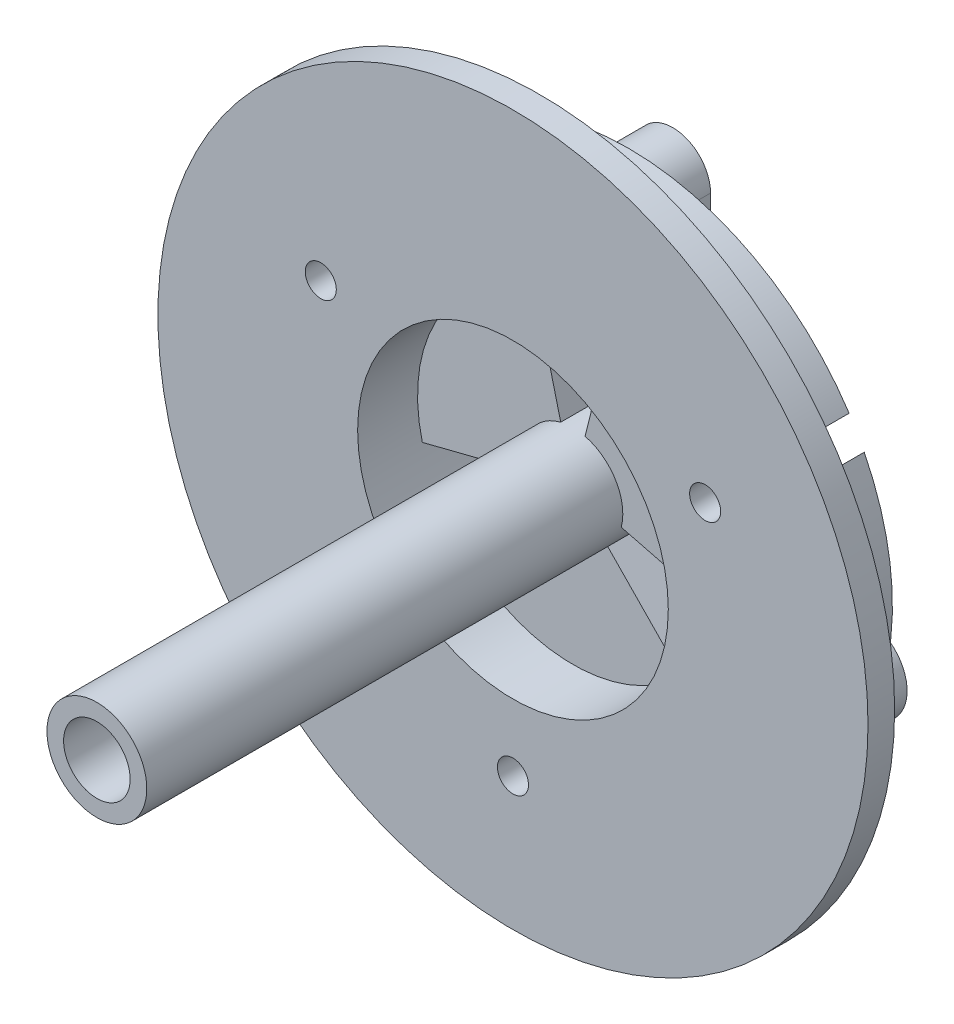
SolidWorks part; units mm, degrees
ref_plane "前视基准面" through (0, 0, 0) normal (0, 0, 1) x (1, 0, 0)
ref_plane "上视基准面" through (0, 0, 0) normal (0, 1, 0) x (1, 0, 0)
ref_plane "右视基准面" through (0, 0, 0) normal (1, 0, 0) x (0, 0, -1)
sketch "草图1" plane through (0, 0, 0) normal (0, 0, 1) x (1, 0, 0)
  circle A0 centre (0, 0) radius 16
extrude "凸台-拉伸1" add sketch "草图1" along normal blind 1.2
sketch "草图2" plane through (0, 0, 1.2) normal (0, 0, 1) x (1, 0, 0)
  circle A0 centre (0, 0) radius 7
extrude "切除-拉伸1" cut sketch "草图2" against normal blind 1.2
sketch "草图3" plane through (0, 0, 1.2) normal (0, 0, 1) x (1, 0, 0)
  circle A2 centre (8.6603, 5) radius 0.7
  circle A3 centre (0, -10) radius 0.7
  circle A4 centre (-8.6603, 5) radius 0.7
extrude "切除-拉伸2" cut sketch "草图3" against normal blind 1.2
sketch "草图4" plane through (0, 0, 0) normal (0, 0, -1) x (-1, 0, 0)
  line L3 (1.7039, 10) -> (1.7039, 5.3952)
  line L16 (-5.5379, -1.0034) -> (-3.6379, -4.2943)
  line L17 (3.6379, -4.2943) -> (5.5379, -1.0034)
  line L18 (1.7039, 5.3952) -> (-1.7039, 5.3952)
  line L19 (-5.5379, -1.0034) -> (-9.6103, -3.3546)
  line L21 (3.6379, -4.2943) -> (7.7103, -6.6454)
  line L25 (-3.6379, -4.2943) -> (-7.7103, -6.6454)
  line L31 (5.5379, -1.0034) -> (9.6103, -3.3546)
  line L32 (-1.7039, 5.3952) -> (-1.7039, 10)
  circle A1 centre (8.6603, -5) radius 0.9
  circle A2 centre (-8.6603, -5) radius 0.9
  circle A3 centre (0, 10) radius 0.9
  arc A4 (1.7039, 10) -> (-1.7039, 10) centre (0, 10) ccw
  arc A5 (7.7103, -6.6454) -> (9.6103, -3.3546) centre (8.6603, -5) ccw
  arc A6 (-9.6103, -3.3546) -> (-7.7103, -6.6454) centre (-8.6603, -5) ccw
extrude "凸台-拉伸2" add sketch "草图4" along normal blind 6
sketch "草图5" plane through (0, 0, 1.2) normal (0, 0, 1) x (1, 0, 0)
  circle A0 centre (0, 0) radius 7
extrude "切除-拉伸3" cut sketch "草图5" against normal blind 11
sketch "草图6" plane through (0, 0, 0) normal (0, 0, -1) x (-1, 0, 0)
  circle A0 centre (0, 0) radius 11.9
  circle A1 centre (0, 0) radius 7
extrude "凸台-拉伸3" add sketch "草图6" along normal blind 4
sketch "草图7" plane through (0, 0, 1.2) normal (0, 0, 1) x (1, 0, 0)
  circle A0 centre (-8.6603, 5) radius 0.7
  circle A1 centre (8.6603, 5) radius 0.7
  circle A2 centre (0, -10) radius 0.7
extrude "切除-拉伸4" cut sketch "草图7" against normal blind 13
sketch "草图8" plane through (0, 0, -4) normal (0, 0, -1) x (-1, 0, 0)
  circle A0 centre (0, 0) radius 2.25
extrude "凸台-拉伸4" add sketch "草图8" against normal blind 33 separate body
sketch "草图9" plane through (0, 0, -4) normal (0, 0, -1) x (-1, 0, 0)
  line L0 (-1.57, -1.6117) -> (-4.8846, -5.0141)
  line L1 (1.57, -1.6117) -> (4.8846, -5.0141)
  line L2 (-2.1808, -0.5539) -> (-6.7846, -1.7232)
  line L3 (-0.5477, 2.1823) -> (-1.7039, 6.7895)
  line L4 (0.5477, 2.1823) -> (1.7039, 6.7895)
  line L5 (2.1808, -0.5539) -> (6.7846, -1.7232)
  arc A0 (-4.8846, -5.0141) -> (4.8846, -5.0141) centre (0, 0) ccw
  arc A1 (-1.7039, 6.7895) -> (-6.7846, -1.7232) centre (0, 0) ccw
  arc A2 (6.7846, -1.7232) -> (1.7039, 6.7895) centre (0, 0) ccw
  arc A3 (2.1808, -0.5539) -> (0.5477, 2.1823) centre (0, 0) ccw
  arc A4 (-1.57, -1.6117) -> (1.57, -1.6117) centre (0, 0) ccw
  arc A5 (-0.5477, 2.1823) -> (-2.1808, -0.5539) centre (0, 0) ccw
extrude "凸台-拉伸5" add sketch "草图9" against normal blind 2.5
sketch "草图10" plane through (0, 0, -4) normal (0, 0, -1) x (-1, 0, 0)
  circle A0 centre (0, 0) radius 1.5
extrude "切除-拉伸5" cut sketch "草图10" against normal blind 33.5
sketch "草图12" plane through (0, 0, 0) normal (1, 0, 0) x (0, 0, -1)
  line L3 (-19.95, -5.0897) -> (-33.7637, -5.0897)
  line L4 (-19.95, -5.0897) -> (-19.95, 5.3715)
  line L5 (-19.95, 5.3715) -> (-33.7637, 5.3715)
  line L6 (-33.7637, -5.0897) -> (-33.7637, 5.3715)
extrude "切除-拉伸6" cut sketch "草图12" against normal mid plane 33.5
sketch "草图13" plane through (0, 0, -4) normal (0, 0, -1) x (-1, 0, 0)
  circle A0 centre (0, -10) radius 2
  circle A1 centre (8.6603, 5) radius 2
  circle A2 centre (-8.6603, 5) radius 2
extrude "切除-拉伸7" cut sketch "草图13" against normal blind 1.5
